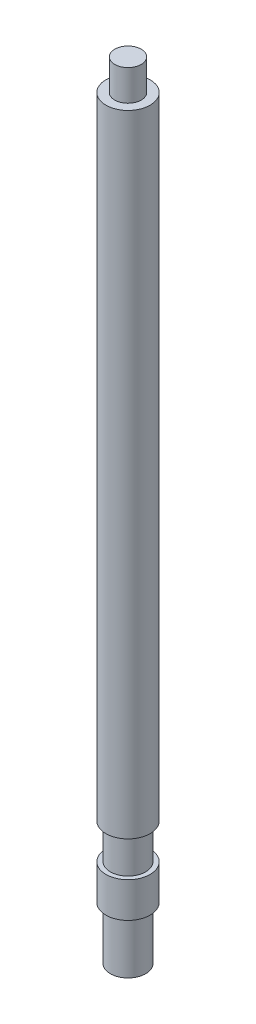
SolidWorks part; units mm, degrees
ref_plane "Front Plane" through (0, 0, 0) normal (0, 0, 1) x (1, 0, 0)
ref_plane "Top Plane" through (0, 0, 0) normal (0, 1, 0) x (1, 0, 0)
ref_plane "Right Plane" through (0, 0, 0) normal (1, 0, 0) x (0, 0, -1)
sketch "Sketch1" plane through (0, 0, 0) normal (0, 1, 0) x (1, 0, 0)
  circle A0 centre (0, 0) radius 5
  dimension "D1" = 10
extrude "Boss-Extrude1" add sketch "Sketch1" along normal blind 143
sketch "Sketch2" plane through (0, 0, 0) normal (0, -1, 0) x (1, 0, 0)
  circle A0 centre (0, 0) radius 4
  dimension "D1" = 8
extrude "Boss-Extrude2" add sketch "Sketch2" along normal blind 8 contours A0
sketch "Sketch3" plane through (0, -8, 0) normal (0, -1, 0) x (1, 0, 0)
  circle A0 centre (0, 0) radius 5
extrude "Boss-Extrude3" add sketch "Sketch3" along normal blind 8
sketch "Sketch4" plane through (0, -16, 0) normal (0, -1, 0) x (1, 0, 0)
  circle A0 centre (0, 0) radius 4
  dimension "D1" = 8
extrude "Boss-Extrude4" add sketch "Sketch4" along normal blind 12
sketch "Sketch5" plane through (0, 143, 0) normal (0, 1, 0) x (1, 0, 0)
  circle A0 centre (0, 0) radius 3
  dimension "D1" = 6
extrude "Boss-Extrude5" add sketch "Sketch5" along normal blind 7
